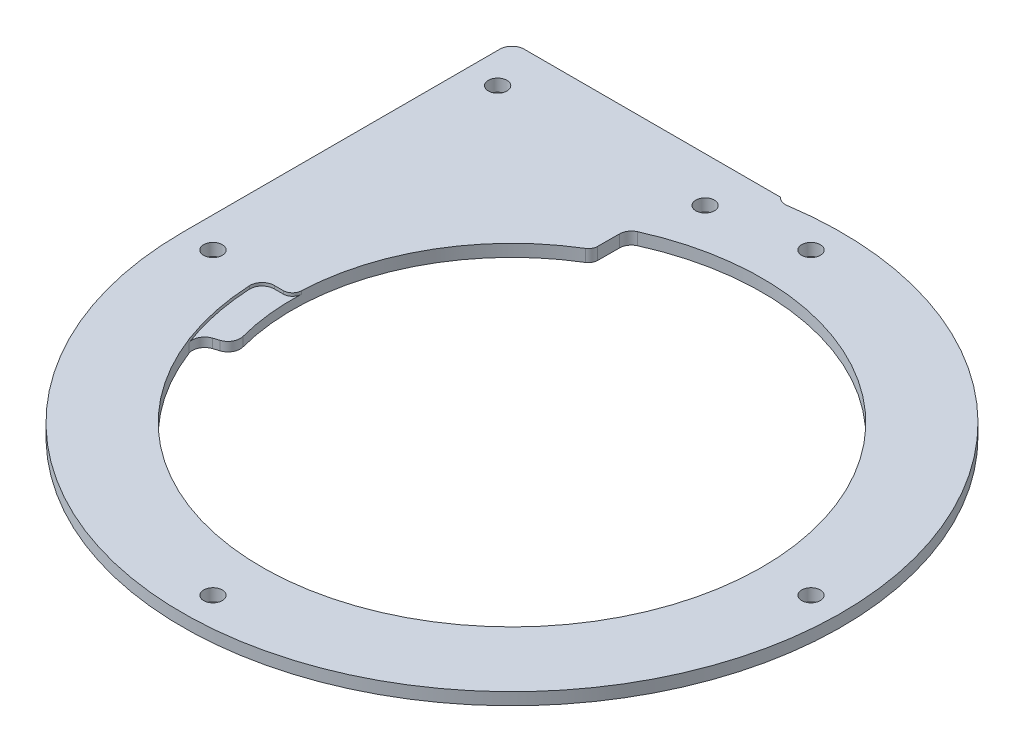
SolidWorks part; units mm, degrees
material "Thornel Mat VMA"
ref_plane "前视基准面" through (0, 0, 0) normal (0, 0, 1) x (1, 0, 0)
ref_plane "上视基准面" through (0, 0, 0) normal (0, 1, 0) x (1, 0, 0)
ref_plane "右视基准面" through (0, 0, 0) normal (1, 0, 0) x (0, 0, -1)
sketch "草图1" plane through (0, 0, 0) normal (0, 1, 0) x (1, 0, 0)
  line L0 (-54, 0) -> (-54, 54)
  line L1 (-54, 54) -> (-10, 54)
  line L2 (-10, 54) -> (-10, 53.066)
  line L3 (-32, 0) -> (-32, 54) construction
  line L4 (-15, 54) -> (-15, 46.6476) construction
  line L5 (-15, 54) -> (-15, 43.7493) construction
  line L6 (-49, 0) -> (-49, 54) construction
  line L7 (-10, 54) -> (-10, 43.7493) construction
  line L8 (-49, 46.6476) -> (-15, 46.6476) construction
  arc A0 (-54, 0) -> (-10, 53.066) centre (0, 0) ccw
  circle A1 centre (0, 0) radius 41
  circle A2 centre (0, 0) radius 32 construction
  circle A4 centre (0, 0) radius 49 construction
  circle A5 centre (-15, 46.6476) radius 1.525
  circle A6 centre (0, 49) radius 1.525
  circle A7 centre (49, 0) radius 1.525
  circle A8 centre (0, -49) radius 1.525
  circle A9 centre (-49, 0) radius 1.525
  circle A20 centre (0, 0) radius 54 construction
  circle A21 centre (-49, 46.6476) radius 1.525
  dimension "D1" = 82
  dimension "D8" = 3.05
  dimension "D4" = 17
  dimension "D2" = 9
  dimension "D3" = 8
  dimension "D5" = 5
  dimension "D7" = 4
extrude "凸台-拉伸1" add sketch "草图1" along normal blind 2
sketch "草图2" plane through (0, 0, 0) normal (0, 1, 0) x (1, 0, 0)
  line L0 (0, 0) -> (-41, 0) construction
  line L1 (-41, 0) -> (-37.47, 0)
  line L2 (0, 0) -> (-49, 0) construction
  line L3 (-18, 31.1769) -> (0, 0) construction
  line L4 (0, 0) -> (-17.9732, 36.8506) construction
  line L5 (-17.996, 32.0266) -> (-17.9732, 36.8506)
  line L6 (-35.9712, 1.44) -> (0, 0) construction
  arc A0 (-18.7161, 30.7523) -> (-35.9712, 1.44) centre (0, 0) ccw
  arc A1 (-17.9732, 36.8506) -> (-41, 0) centre (0, 0) ccw
  circle A2 centre (0, 0) radius 41 construction
  arc A6 (-35.9712, 1.44) -> (-37.47, 0) centre (-37.47, 1.5) cw
  arc A7 (-18.7161, 30.7523) -> (-17.996, 32.0266) centre (-19.496, 32.0337) ccw
  dimension "D1" = 72
  dimension "D4" = 1.5
  dimension "D5" = 1.5
  dimension "D6" = 60
  dimension "D7" = 4
extrude "凸台-拉伸3" add sketch "草图2" along normal up to surface (2 mm away) up to face at (-49, 2, 1.525)
fillet "圆角1" radius 2 2 edges at (-17.9732, 1, -36.8506) (-41, 1, 0)
sketch "草图3" plane through (0, 2, 0) normal (0, 1, 0) x (1, 0, 0)
  line L1 (-54, 54) -> (-10, 54)
  line L2 (-54, 54) -> (-54, 59)
  line L3 (-54, 59) -> (-10, 59)
  line L4 (-10, 54) -> (-10, 59)
  dimension "D1" = 5
extrude "凸台-拉伸4" [suppressed] add sketch "草图3" against normal blind 1.5
fillet "圆角2" radius 2 2 edges at (-10, 1, -53.066) (-54, 1, -54)
sketch "草图4" plane through (0, 0, 0) normal (0, -1, 0) x (1, 0, 0)
  line L0 (-38.9487, 0) -> (-37.47, 0) construction
  line L1 (-38.9487, 0) -> (-37.47, 0)
  line L2 (0, 0) -> (-37.47, 0) construction
  line L3 (-34.238, 11.1246) -> (-38.9933, 12.6697)
  line L4 (-34.238, 11.1246) -> (0, 0) construction
  arc A0 (-40.9461, 2.1026) -> (-38.9487, 0) centre (-38.9487, 2) ccw construction
  arc A1 (-35.9712, -1.44) -> (-37.47, 0) centre (-37.47, -1.5) ccw construction
  arc A2 (-40.9461, 2.1026) -> (-38.9487, 0) centre (-38.9487, 2) ccw
  arc A3 (-35.9712, -1.44) -> (-37.47, 0) centre (-37.47, -1.5) ccw
  arc A4 (-34.238, 11.1246) -> (-35.9712, -1.44) centre (0, 0) ccw
  arc A5 (-16.7987, -37.4006) -> (-40.9461, 2.1026) centre (0, 0) ccw construction
  arc A6 (-38.9933, 12.6697) -> (-40.9461, 2.1026) centre (0, 0) ccw
  dimension "D1" = 18
extrude "凸台-拉伸5" add sketch "草图4" against normal blind 1.5
fillet "圆角3" radius 2 2 edges at (-34.238, 0.75, 11.1246) (-38.9933, 0.75, 12.6697)
